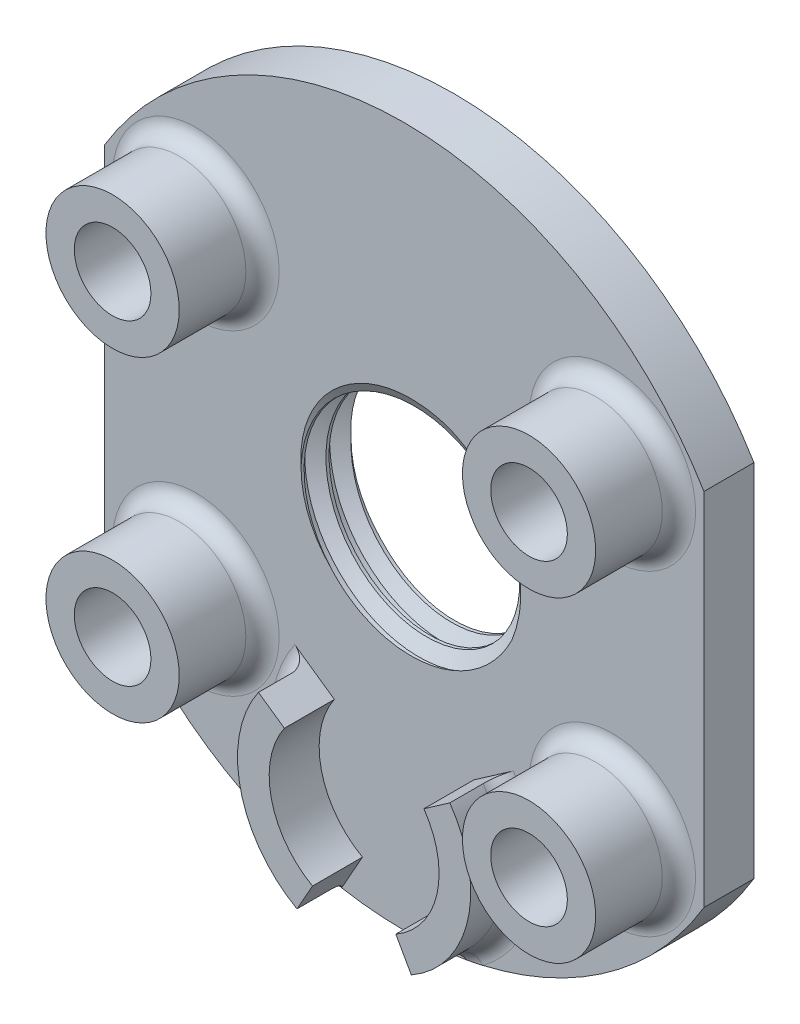
SolidWorks part; units mm, degrees
ref_plane "Plan de face" through (0, 0, 0) normal (0, 0, 1) x (1, 0, 0)
ref_plane "Plan de dessus" through (0, 0, 0) normal (0, 1, 0) x (1, 0, 0)
ref_plane "Plan de droite" through (0, 0, 0) normal (1, 0, 0) x (0, 0, -1)
sketch "Base" plane through (0, 0, 0) normal (0, 0, 1) x (1, 0, 0)
  line L0 (-29.422, -21) -> (29.0469, -21) construction
  line L1 (-12.5, -9.5) -> (12.5, -9.5) construction
  line L2 (-12.5, -9.5) -> (-12.5, 9.5) construction
  line L3 (-12.5, 9.5) -> (12.5, 9.5) construction
  line L4 (12.5, -9.5) -> (12.5, 9.5) construction
  line L5 (-12.5, -9.5) -> (12.5, 9.5) construction
  line L6 (-12.5, 9.5) -> (12.5, -9.5) construction
  circle A0 centre (0, 0) radius 21
  point P0 (0, 0)
  dimension "D1" = 42
  dimension "D2" = 25
  dimension "D3" = 19
extrude "Boss.-Extru.1_Base" add sketch "Base" along normal blind 3
sketch "Tap_Drill_Hole" plane through (0, 0, 3) normal (0, 0, 1) x (1, 0, 0)
  circle A0 centre (0, 0) radius 6.188
  circle A1 centre (0, 0) radius 6.188 construction
  circle A2 centre (0, 0) radius 6.188 construction
  dimension "D1" = 12.376
extrude "Enlèv. mat.-Extru.1_Tap_Drill_Hole" cut sketch "Tap_Drill_Hole" against normal up to next
sketch "Esquisse3" plane through (0, 0, 3) normal (0, 0, 1) x (1, 0, 0)
  circle A0 centre (0, 0) radius 6.188 construction
  circle A1 centre (0, 0) radius 6.188
curve "Hélice/Spirale1" pitch 1.5 height 4.5 radius 6.188 centre (0, 0, 3) axis (0, 0, -1) start towards (-1, 0, 0)
sketch "Dents" plane through (0, 0, 0) normal (0, 1, 0) x (1, 0, 0)
  line L0 (-6.188, -4.3126) -> (-6.188, -3)
  line L1 (-6.188, -3) -> (-7, -3.4688)
  line L2 (-7.3248, -3.6563) -> (-7, -3.8438) construction
  line L3 (-7, -3.8438) -> (-7, -3.4688)
  line L4 (-7, -3.8438) -> (-6.188, -4.3126)
  line L5 (-7, -3.4688) -> (-7.3248, -3.6563) construction
  line L6 (-6.188, 0) -> (-6.188, -3) construction
  dimension "D1" = 0.812
  dimension "D2" = 0.375
  dimension "D3" = 60
sweep "Enlèvement de matière-Balayage1" cut profiles "Dents" path "Hélice/Spirale1" align with end faces yes
sketch "Notch" plane through (0, 0, 3) normal (0, 0, 1) x (1, 0, 0)
  line L1 (-12.5196, -16.86) -> (12.5196, -16.86)
  line L2 (-12.5196, -16.86) -> (-12.5196, -21)
  line L3 (-12.5196, -21) -> (12.5196, -21)
  line L4 (12.5196, -16.86) -> (12.5196, -21)
  line L5 (-12.5196, -16.86) -> (12.5196, -21) construction
  line L6 (-12.5196, -21) -> (12.5196, -16.86) construction
  circle A0 centre (0, 0) radius 21 construction
  point P4 (0, -18.93)
  dimension "D1" = 4.14
extrude "Enlèv. mat.-Extru.2_Notch" [suppressed] cut sketch "Notch" against normal up to next
sketch "Entretoise" plane through (0, 0, 3) normal (0, 0, 1) x (1, 0, 0)
  line L0 (0, 0) -> (-12.5, -9.5) construction
  line L1 (-18.105, -8.7357) -> (-13.2643, -15.105) construction
  line L2 (-18.105, -8.7357) -> (-14.9203, -6.3154) construction
  line L3 (-13.2643, -15.105) -> (-10.0797, -12.6846) construction
  circle A0 centre (-12.5, 9.5) radius 5.2997 construction
  circle A1 centre (12.5, 9.5) radius 5.2997 construction
  circle A2 centre (-12.5, -9.5) radius 5.2997 construction
  circle A3 centre (12.5, -9.5) radius 5.2997 construction
  circle A4 centre (0, 0) radius 21 construction
  circle A5 centre (-12.5, -9.5) radius 4 construction
  circle A8 centre (-12.5, -9.5) radius 4
  dimension "D1" = 8
extrude "Boss.-Extru.2_Entretoise" add sketch "Entretoise" along normal blind 5
mirror "Symétrie1_Entretoises_Vertical" about plane through (0, 0, 0) normal (1, 0, 0) of "Boss.-Extru.2_Entretoise"
mirror "Symétrie1__Entretoises_Horizontal" about plane through (0, 0, 0) normal (0, 1, 0) of "Symétrie1_Entretoises_Vertical", "Boss.-Extru.2_Entretoise"
sketch "Trous_Entretoises" plane through (0, 0, 8) normal (0, 0, 1) x (1, 0, 0)
  circle A0 centre (-12.5, 9.5) radius 2.3
  circle A1 centre (12.5, 9.5) radius 2.3
  circle A2 centre (-12.5, -9.5) radius 2.3
  circle A3 centre (12.5, -9.5) radius 2.3
  dimension "D1" = 4.6
extrude "Enlèv. mat.-Extru.3_Trous_Entretoises" cut sketch "Trous_Entretoises" against normal blind 5
sketch "Trous_Vis_M2" plane through (0, 0, 0) normal (0, 0, -1) x (-1, 0, 0)
  circle A0 centre (-12.5, -9.5) radius 1.25
  circle A1 centre (12.5, -9.5) radius 1.25 construction
  circle A2 centre (-12.5, 9.5) radius 1.25 construction
  circle A3 centre (12.5, 9.5) radius 1.25
  dimension "D1" = 2.5
extrude "Enlèv. mat.-Extru.4_Trous_Vis_M2" cut sketch "Trous_Vis_M2" against normal up to next
sketch "Contour_Support_Moteur" plane through (0, 0, 3) normal (0, 0, 1) x (1, 0, 0)
  line L0 (0, -21) -> (0, -6.188) construction
  line L1 (0, -21) -> (0, -10) construction
  line L2 (0, -5.225) -> (0, 5.225) construction
  line L3 (-5.7446, -10) -> (5.7446, -10) construction
  line L4 (-5.7446, -10) -> (-4.1853, -11.0857) construction
  line L5 (2.5, -18.4452) -> (3.4314, -20.1013) construction
  line L6 (-2.5, -14) -> (2.5, -14) construction
  line L7 (-2.5, -14) -> (-2.5, -18.4452) construction
  line L8 (2.5, -14) -> (2.5, -18.4452) construction
  line L9 (-3.4314, -20.1013) -> (-2.5, -18.4452) construction
  line L10 (5.7446, -10) -> (4.1853, -11.0857) construction
  line L11 (-5.7446, -10) -> (-4.1853, -11.0857)
  line L12 (-2.5, -18.4452) -> (-3.4314, -20.1013)
  line L13 (4.1853, -11.0857) -> (5.7446, -10)
  line L14 (3.4314, -20.1013) -> (2.5, -18.4452)
  circle A1 centre (0, 0) radius 6.188 construction
  circle A2 centre (0, 0) radius 6.188 construction
  circle A3 centre (0, 0) radius 21 construction
  circle A4 centre (0, 0) radius 21 construction
  arc A5 (-5.7446, -10) -> (5.7446, -10) centre (0, -14) ccw construction
  circle A6 centre (0, -14) radius 5.1 construction
  arc A7 (-4.1853, -11.0857) -> (-2.5, -18.4452) centre (0, -14) ccw
  arc A8 (-3.4314, -20.1013) -> (-5.7446, -10) centre (0, -14) cw
  arc A9 (5.7446, -10) -> (3.4314, -20.1013) centre (0, -14) cw
  arc A10 (2.5, -18.4452) -> (4.1853, -11.0857) centre (0, -14) ccw
  point P20 (0, -14)
  dimension "D1" = 7
  dimension "D3" = 10.2
  dimension "D2" = 11
  dimension "D4" = 5
extrude "Boss.-Extru.1_Contour_Support_Moteur" add sketch "Contour_Support_Moteur" along normal blind 3
fillet "Congé2_1mm" radius 1 6 edges at (-8.5, -9.5, 3) (16.5, -9.5, 3) (8.5, 9.5, 3) (-8.5, 9.5, 3) (6.8234, -15.5625, 3) (-6.8234, -15.5625, 3)
sketch "Arêtes" plane through (0, 0, 3) normal (0, 0, 1) x (1, 0, 0)
  line L0 (-18, 10.8167) -> (-18, -10.8167)
  line L1 (-18, -21) -> (18, -21) construction
  line L2 (-18, -21) -> (-18, 21) construction
  line L3 (-18, 21) -> (18, 21) construction
  line L4 (18, -21) -> (18, 21) construction
  line L5 (-18, -21) -> (18, 21) construction
  line L6 (-18, 21) -> (18, -21) construction
  line L7 (18, 10.8167) -> (18, -10.8167)
  arc A0 (4.7131, -20.4643) -> (-4.7131, -20.4643) centre (0, 0) ccw construction
  arc A1 (-18, 10.8167) -> (-18, -10.8167) centre (0, 0) ccw
  arc A2 (18, 10.8167) -> (18, -10.8167) centre (0, 0) cw
  point P0 (0, 0)
  dimension "D1" = 36
extrude "Enlèv. mat.-Extru.1_Arêtes" cut sketch "Arêtes" against normal up to next
